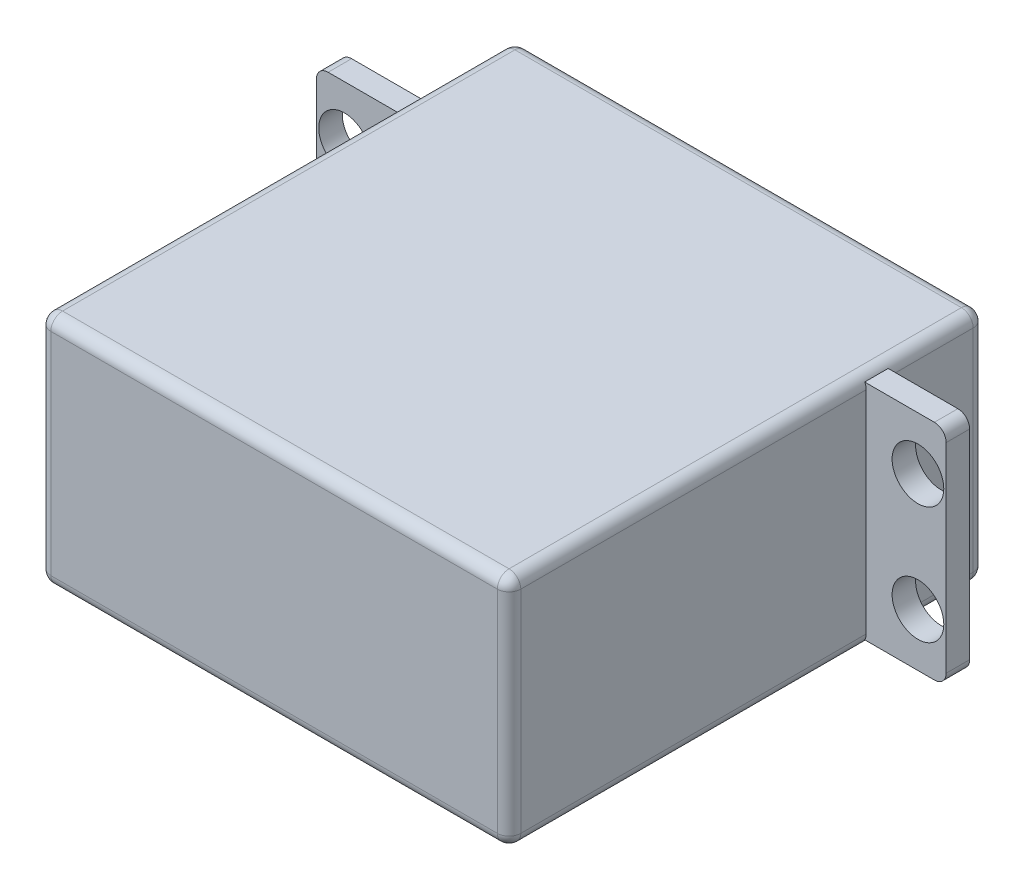
SolidWorks part; units mm, degrees
ref_plane "Front Plane" through (0, 0, 0) normal (0, 0, 1) x (1, 0, 0)
ref_plane "Top Plane" through (0, 0, 0) normal (0, 1, 0) x (1, 0, 0)
ref_plane "Right Plane" through (0, 0, 0) normal (1, 0, 0) x (0, 0, -1)
sketch "Sketch1" plane through (0, 0, 0) normal (0, 0, 1) x (1, 0, 0)
  line L1 (-20, -10) -> (20, -10)
  line L2 (-20, -10) -> (-20, 10)
  line L3 (-20, 10) -> (20, 10)
  line L4 (20, -10) -> (20, 10)
  line L5 (-20, -10) -> (20, 10) construction
  line L6 (-20, 10) -> (20, -10) construction
  point P0 (0, 0)
extrude "Boss-Extrude1" add sketch "Sketch1" along normal blind 40.5
ref_plane "Plane1" through (0, 0, 10.1) normal (0, 0, 1) x (1, 0, 0)
sketch "Sketch2" plane through (0, 0, 10.1) normal (0, 0, 1) x (1, 0, 0)
  line L1 (26.8, -9.5) -> (-26.8, -9.5)
  line L2 (26.8, -9.5) -> (26.8, 9.5)
  line L3 (26.8, 9.5) -> (-26.8, 9.5)
  line L4 (-26.8, -9.5) -> (-26.8, 9.5)
  line L5 (26.8, -9.5) -> (-26.8, 9.5) construction
  line L6 (26.8, 9.5) -> (-26.8, -9.5) construction
  point P0 (0, 0)
extrude "Boss-Extrude2" add sketch "Sketch2" against normal blind 2
sketch "Sketch3" plane through (0, 0, 10.1) normal (0, 0, 1) x (1, 0, 0)
  line L1 (-24.4, 5) -> (24.4, 5) construction
  line L2 (-24.4, 5) -> (-24.4, -5) construction
  line L3 (-24.4, -5) -> (24.4, -5) construction
  line L4 (24.4, 5) -> (24.4, -5) construction
  line L5 (-24.4, 5) -> (24.4, -5) construction
  line L6 (-24.4, -5) -> (24.4, 5) construction
  circle A0 centre (-24.4, 5) radius 2.2
  circle A1 centre (-24.4, -5) radius 2.2
  circle A2 centre (24.4, 5) radius 2.2
  circle A3 centre (24.4, -5) radius 2.2
  point P0 (0, 0)
extrude "Cut-Extrude1" cut sketch "Sketch3" against normal blind 2
sketch "Sketch4" plane through (0, 0, 0) normal (0, 0, -1) x (-1, 0, 0)
  line L0 (26.8, 0) -> (10, 0) construction
  line L1 (26.8, 9.5) -> (26.8, -9.5) construction
  circle A0 centre (10, 0) radius 3
  circle A1 centre (10, 0) radius 1
extrude "Boss-Extrude3" add sketch "Sketch4" along normal blind 4
fillet "Fillet1" radius 1 8 edges at (-26.8, -9.5, 9.1) (-26.8, 9.5, 9.1) (26.8, 9.5, 9.1) (26.8, -9.5, 9.1) (-20, 10, 20.25) (20, 10, 20.25) (-20, -10, 20.25) (20, -10, 20.25)
fillet "Fillet2" radius 1 16 edges at (19.7071, 9.7071, 40.5) (20, 0, 40.5) (19.7071, -9.7071, 40.5) (0, -10, 40.5) (-19.7071, -9.7071, 40.5) (-20, 0, 40.5) (-19.7071, 9.7071, 40.5) (19.7071, 9.7071, 0) (20, 0, 0) (19.7071, -9.7071, 0) (0, -10, 0) (-19.7071, -9.7071, 0) (-20, 0, 0) (-19.7071, 9.7071, 0) (0, 10, 40.5) (0, 10, 0)
